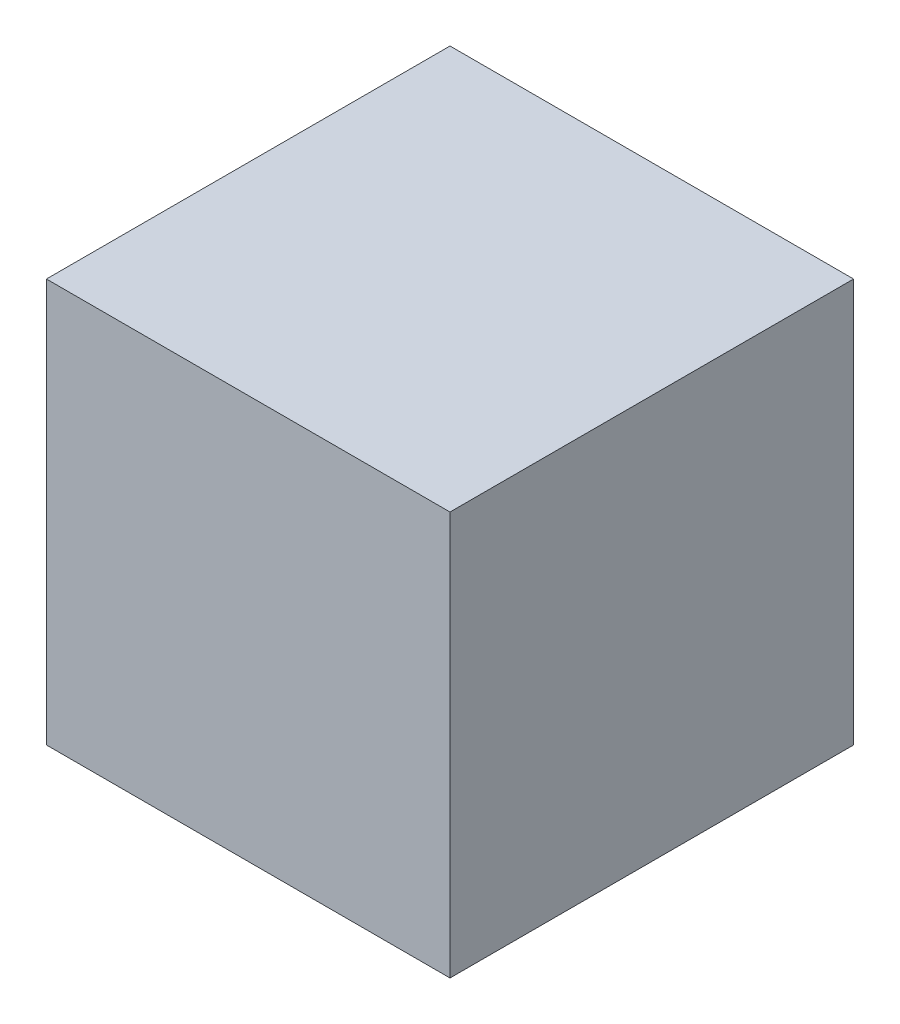
SolidWorks part; units mm, degrees
ref_plane "Front" through (0, 0, 0) normal (0, 0, 1) x (1, 0, 0)
ref_plane "Top" through (0, 0, 0) normal (0, 1, 0) x (1, 0, 0)
ref_plane "Right" through (0, 0, 0) normal (1, 0, 0) x (0, 0, -1)
sketch "Sketch1" plane through (0, 0, 0) normal (0, 0, 1) x (1, 0, 0)
  line L1 (-1066.8, -1066.8) -> (1066.8, -1066.8)
  line L2 (-1066.8, -1066.8) -> (-1066.8, 1066.8)
  line L3 (-1066.8, 1066.8) -> (1066.8, 1066.8)
  line L4 (1066.8, -1066.8) -> (1066.8, 1066.8)
  line L5 (-1066.8, -1066.8) -> (1066.8, 1066.8) construction
  line L6 (-1066.8, 1066.8) -> (1066.8, -1066.8) construction
  point P0 (0, 0)
  dimension "D1" = 2133.6
  dimension "D2" = 2133.6
extrude "Boss-Extrude1" add sketch "Sketch1" along normal mid plane 2133.6
shell "Shell1" thickness 304.8
ref_axis "Axis1" through (0, 0, 0) along (0, 1, 0)
ref_axis "Axis2" through (0, 0, 0) along (0, 0, 1)
equation "\"outer_height\"=84"
equation "\"D1@Sketch1\"=\"outer_height\""
equation "\"outer_width\"=84"
equation "\"D2@Sketch1\"=\"outer_width\""
equation "\"outer_depth\"=84"
equation "\"D1@Boss-Extrude1\"=\"outer_depth\""
